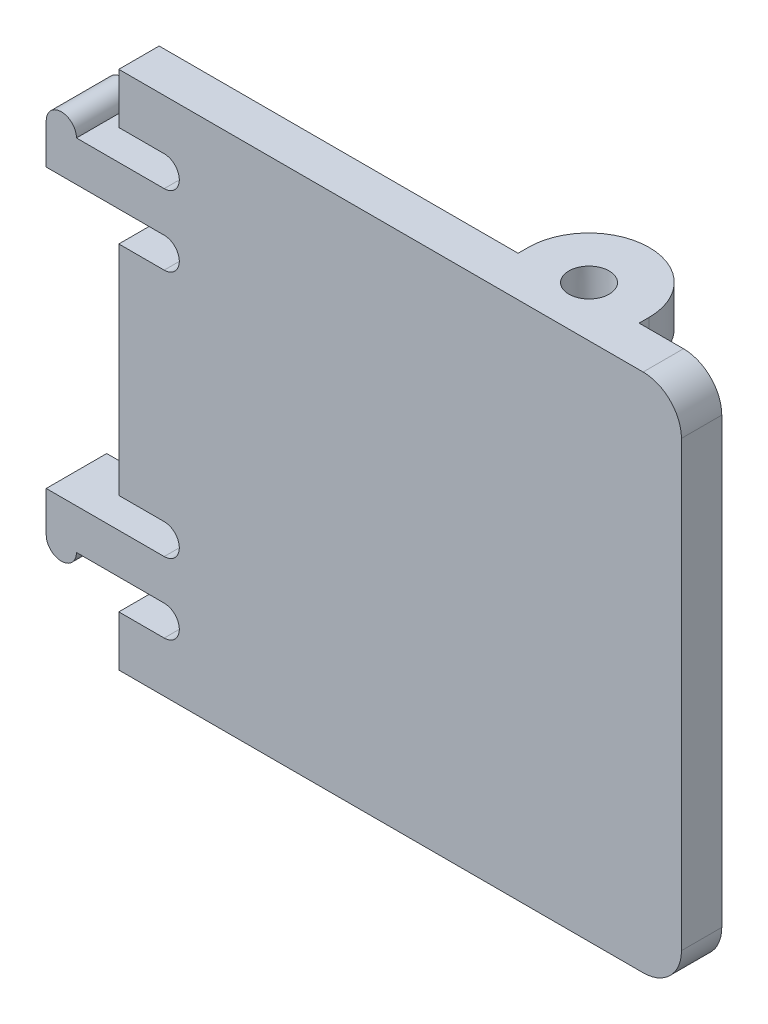
SolidWorks part; units mm, degrees
ref_plane "前视基准面" through (0, 0, 0) normal (0, 0, 1) x (1, 0, 0)
ref_plane "上视基准面" through (0, 0, 0) normal (0, 1, 0) x (1, 0, 0)
ref_plane "右视基准面" through (0, 0, 0) normal (1, 0, 0) x (0, 0, -1)
other "Configuration Table"
sketch "草图1" plane through (0, 0, 0) normal (0, 0, 1) x (1, 0, 0)
  line L3 (-11.9424, 3.3113) -> (-11.9424, -22.4887)
  line L4 (-11.9424, 37.4113) -> (-11.9424, -25.5887) construction
  line L6 (-11.9424, -22.4887) -> (14.0576, -22.4887)
  line L7 (15.9576, -20.5887) -> (15.9576, 1.4113)
  line L8 (14.0576, 3.3113) -> (-11.9424, 3.3113)
  line L9 (-11.9424, -22.4887) -> (14.0576, -22.4887)
  line L10 (15.9576, -20.5887) -> (15.9576, 1.4113)
  line L11 (14.0576, 3.3113) -> (-11.9424, 3.3113)
  arc A4 (14.0576, -22.4887) -> (15.9576, -20.5887) centre (14.0576, -20.5887) ccw
  arc A5 (15.9576, 1.4113) -> (14.0576, 3.3113) centre (14.0576, 1.4113) ccw
  arc A6 (14.0576, -22.4887) -> (15.9576, -20.5887) centre (14.0576, -20.5887) ccw
  arc A7 (15.9576, 1.4113) -> (14.0576, 3.3113) centre (14.0576, 1.4113) ccw
  dimension "D1" = 0.1
extrude "凸台-拉伸1" add sketch "草图1" against normal blind 2
sketch "草图2" plane through (0, 0, -2) normal (0, 0, -1) x (-1, 0, 0)
  line L0 (11.9424, -22.4887) -> (-14.0576, -22.4887) construction
  line L1 (-5.8576, -22.4887) -> (-11.8576, -22.4887)
  line L2 (-5.8576, -22.4887) -> (-5.8576, -20.4887)
  line L3 (-5.8576, -20.4887) -> (-11.8576, -20.4887)
  line L4 (-11.8576, -22.4887) -> (-11.8576, -20.4887)
  line L5 (-14.0576, 3.3113) -> (11.9424, 3.3113) construction
  line L6 (-5.8576, 3.3113) -> (-11.8576, 3.3113)
  line L7 (-5.8576, 3.3113) -> (-5.8576, 1.3113)
  line L8 (-5.8576, 1.3113) -> (-11.8576, 1.3113)
  line L9 (-11.8576, 3.3113) -> (-11.8576, 1.3113)
  line L10 (-18.0576, -20.5887) -> (-18.0576, 1.4113) construction
  dimension "D1" = 6
  dimension "D2" = 6.2
  dimension "D3" = 2
extrude "凸台-拉伸2" add sketch "草图2" along normal blind 3.5
fillet "圆角1" radius 3 4 edges at (11.8576, 2.3113, -5.5) (5.8576, 2.3113, -5.5) (11.8576, -21.4887, -5.5) (5.8576, -21.4887, -5.5)
sketch "草图3" plane through (0, -22.4887, 0) normal (0, -1, 0) x (1, 0, 0)
  circle A0 centre (8.8741, -2.5) radius 1
  dimension "D1" = 2
extrude "切除-拉伸1" cut sketch "草图3" against normal blind 5 draft 2
sketch "草图4" plane through (0, 3.3113, 0) normal (0, 1, 0) x (1, 0, 0)
  circle A0 centre (8.8741, 2.5) radius 1
  dimension "D1" = 2
extrude "切除-拉伸2" cut sketch "草图4" against normal blind 5 draft 2
sketch "草图6" plane through (0, 0, 0) normal (0, 0, 1) x (1, 0, 0)
  line L0 (-11.9424, 3.3113) -> (-11.9424, -22.4887) construction
  line L1 (-11.9424, -0.6887) -> (-15.5424, -0.6887)
  line L2 (-11.9424, -0.6887) -> (-11.9424, -2.6887)
  line L3 (-11.9424, -2.6887) -> (-15.5424, -2.6887)
  line L4 (-15.5424, -0.6887) -> (-15.5424, -2.6887)
  line L5 (14.0576, 3.3113) -> (-11.9424, 3.3113) construction
  line L6 (-11.9424, -18.4887) -> (-15.5424, -18.4887)
  line L7 (-11.9424, -18.4887) -> (-11.9424, -16.4887)
  line L8 (-11.9424, -16.4887) -> (-15.5424, -16.4887)
  line L9 (-15.5424, -18.4887) -> (-15.5424, -16.4887)
  line L10 (-11.9424, -22.4887) -> (14.0576, -22.4887) construction
  dimension "D1" = 2
  dimension "D2" = 4
  dimension "D3" = 4
  dimension "D4" = 3.6
extrude "凸台-拉伸3" add sketch "草图6" against normal blind 3
chamfer "倒角1" distance 3 angle 45 2 edges at (-11.9424, -17.4887, -2) (-11.9424, -1.6887, -2)
sketch "草图7" plane through (0, 0, 0) normal (0, 0, 1) x (1, 0, 0)
  line L0 (-15.5424, -0.6887) -> (-15.5424, -2.6887) construction
  line L1 (-15.5424, -2.6887) -> (-11.9424, -2.6887) construction
  line L2 (-15.5424, -16.4887) -> (-15.5424, -18.4887) construction
  line L3 (-11.9424, -16.4887) -> (-15.5424, -16.4887) construction
  circle A0 centre (-14.7924, -0.6887) radius 0.75
  circle A1 centre (-14.7924, -18.4887) radius 0.75
  dimension "D1" = 1.5
  dimension "D3" = 2
  dimension "D2" = 2
extrude "凸台-拉伸4" add sketch "草图7" against normal blind 3
sketch "草图8" plane through (0, 0, 0) normal (0, 0, 1) x (1, 0, 0)
  line L1 (-11.9424, -0.6887) -> (-8.9424, -0.6887)
  line L2 (-11.9424, -0.6887) -> (-11.9424, 0.8113)
  line L3 (-11.9424, 0.8113) -> (-8.9424, 0.8113)
  line L4 (-8.9424, -0.6887) -> (-8.9424, 0.8113)
  line L5 (-11.9424, -2.6887) -> (-8.9424, -2.6887)
  line L6 (-11.9424, -2.6887) -> (-11.9424, -4.1887)
  line L7 (-11.9424, -4.1887) -> (-8.9424, -4.1887)
  line L8 (-8.9424, -2.6887) -> (-8.9424, -4.1887)
  line L9 (-11.9424, -16.4887) -> (-8.9424, -16.4887)
  line L10 (-11.9424, -16.4887) -> (-11.9424, -14.9887)
  line L11 (-11.9424, -14.9887) -> (-8.9424, -14.9887)
  line L12 (-8.9424, -16.4887) -> (-8.9424, -14.9887)
  line L13 (-11.9424, -18.4887) -> (-8.9424, -18.4887)
  line L14 (-11.9424, -18.4887) -> (-11.9424, -19.9887)
  line L15 (-11.9424, -19.9887) -> (-8.9424, -19.9887)
  line L16 (-8.9424, -18.4887) -> (-8.9424, -19.9887)
  dimension "D1" = 1.5
  dimension "D2" = 3
extrude "切除-拉伸3" cut sketch "草图8" against normal up to next
fillet "圆角2" radius 0.75 8 edges at (-8.9424, -19.9887, -1) (-8.9424, -18.4887, -1) (-8.9424, -16.4887, -1) (-8.9424, -14.9887, -1) (-8.9424, -2.6887, -1) (-8.9424, -4.1887, -1) (-8.9424, -0.6887, -1) (-8.9424, 0.8113, -1)
